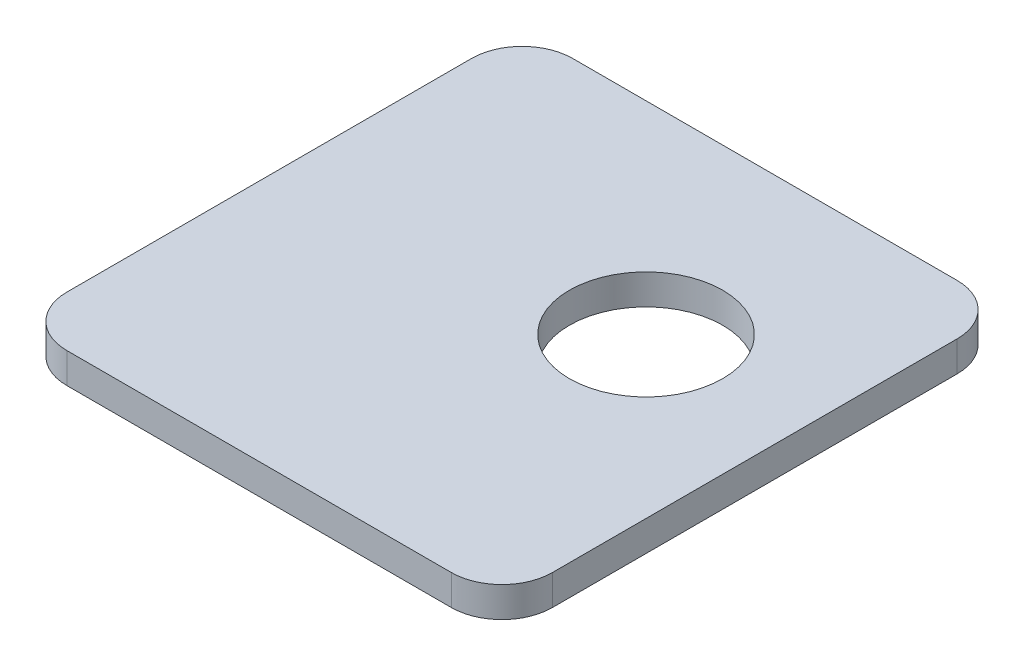
SolidWorks part; units mm, degrees
material "Acrylic (Medium-high impact)"
ref_plane "Front Plane" through (0, 0, 0) normal (0, 0, 1) x (1, 0, 0)
ref_plane "Top Plane" through (0, 0, 0) normal (0, 1, 0) x (1, 0, 0)
ref_plane "Right Plane" through (0, 0, 0) normal (1, 0, 0) x (0, 0, -1)
sketch "Sketch1" plane through (0, 0, 0) normal (0, 1, 0) x (1, 0, 0)
  line L1 (-19.4223, 29.2067) -> (18.5777, 29.2067)
  line L2 (-24.4223, 24.2067) -> (-24.4223, -15.7933)
  line L3 (-19.4223, -20.7933) -> (18.5777, -20.7933)
  line L4 (23.5777, 24.2067) -> (23.5777, -15.7933)
  arc A0 (-24.4223, 24.2067) -> (-19.4223, 29.2067) centre (-19.4223, 24.2067) cw
  arc A1 (-24.4223, -15.7933) -> (-19.4223, -20.7933) centre (-19.4223, -15.7933) ccw
  arc A2 (23.5777, -15.7933) -> (18.5777, -20.7933) centre (18.5777, -15.7933) cw
  arc A3 (23.5777, 24.2067) -> (18.5777, 29.2067) centre (18.5777, 24.2067) ccw
  circle A6 centre (7.8247, 9.2083) radius 7.575
  circle A7 centre (7.8247, 9.2083) radius 7.575
  point P6 (-24.4223, 29.2067)
  point P9 (-24.4223, -20.7933)
  point P14 (23.5777, 29.2067)
  dimension "D3" = 5
  dimension "D1" = 50
  dimension "D2" = 48
  dimension "D4" = 0.25
extrude "Boss-Extrude1" add sketch "Sketch1" along normal blind 3
